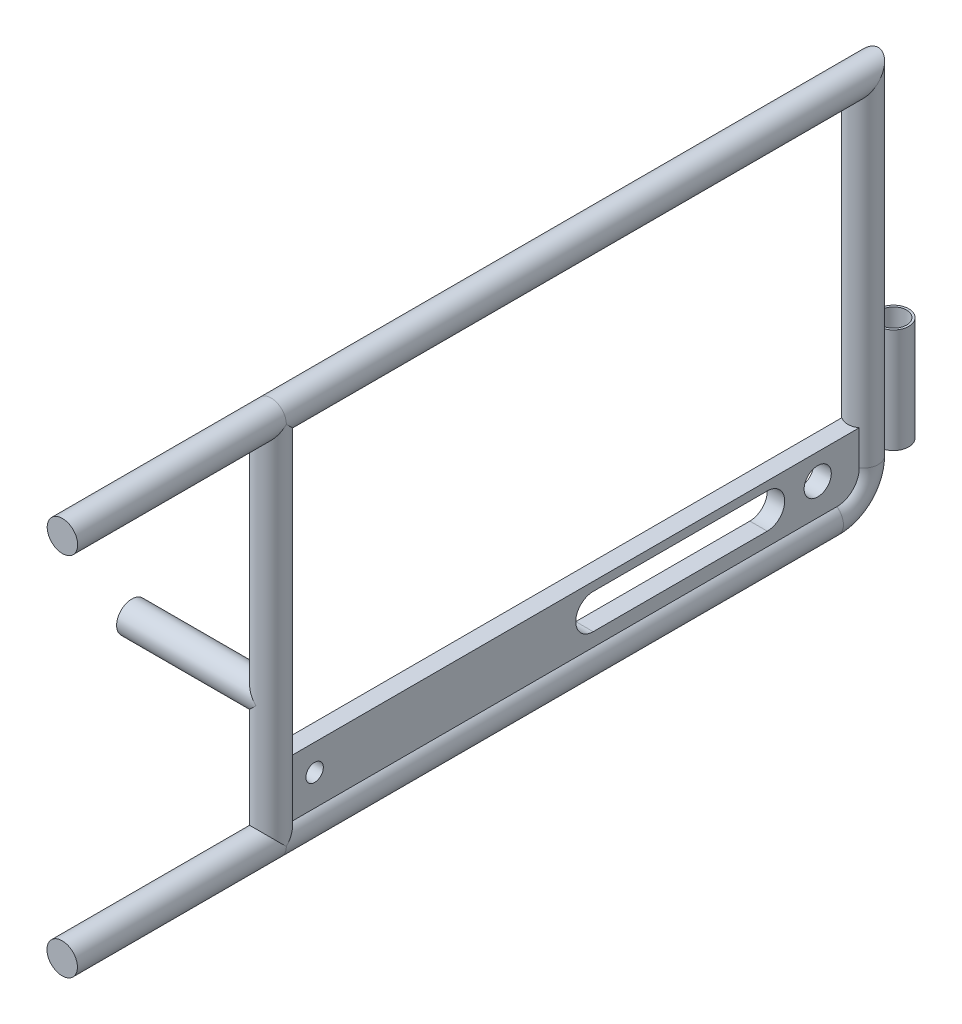
SolidWorks part; units mm, degrees
note: The reader was unsure of these and kept them because the rebuilt part matched: shared geometry of "Sketch3<8>", "Sketch1<23>".
ref_plane "Front Plane" through (0, 0, 0) normal (0, 0, 1) x (1, 0, 0)
ref_plane "Top Plane" through (0, 0, 0) normal (0, 1, 0) x (1, 0, 0)
ref_plane "Right Plane" through (0, 0, 0) normal (1, 0, 0) x (0, 0, -1)
sketch "Sketch1" plane through (0, 0, 0) normal (1, 0, 0) x (0, 0, -1)
  line L0 (126.1633, -30.1592) -> (152.2128, -152.4)
  line L2 (152.2128, -431.8) -> (584.0128, -431.8)
  line L4 (584.0128, -673.1) -> (584.0128, -431.8)
  line L5 (152.2128, -431.8) -> (0, -431.8)
  line L6 (558.6128, -698.5) -> (152.2128, -698.5)
  line L7 (88.9, 0) -> (0, 0)
  line L8 (152.2128, -152.4) -> (431.6128, -152.4)
  line L10 (457.0128, -177.8) -> (457.0128, -273.05)
  line L16 (457.0128, -273.05) -> (558.6128, -273.05)
  line L17 (584.0128, -298.45) -> (584.0128, -431.8)
  line L18 (-0.1872, -698.5) -> (152.2128, -698.5)
  line L19 (152.2128, -698.5) -> (152.2128, -431.8)
  line L20 (152.2128, -152.4) -> (152.2128, -431.8)
  arc A0 (88.9, 0) -> (126.1633, -30.1592) centre (88.9, -38.1) cw
  arc A1 (584.0128, -673.1) -> (558.6128, -698.5) centre (558.6128, -673.1) cw
  arc A2 (584.0128, -298.45) -> (558.6128, -273.05) centre (558.6128, -298.45) ccw
  arc A3 (431.6128, -152.4) -> (457.0128, -177.8) centre (431.6128, -177.8) cw
  point P5 (584.0128, -698.5)
  point P24 (584.0128, -273.05)
  point P30 (457.0128, -152.4)
  dimension "D2" = 38.1
  dimension "D11" = 25.4
  dimension "D9" = 25.4
  dimension "D1" = 88.9
  dimension "D3" = 120.65
  dimension "D4" = 431.8
  dimension "D5" = 431.8
  dimension "D6" = 279.4
  dimension "D7" = 152.4
  dimension "D8" = 546.1
  dimension "D10" = 127
  dimension "D17" = 124.9856
sketch "Sketch3" plane through (0, 0, 0) normal (0, 0, 1) x (1, 0, 0)
  circle A0 centre (0, -698.5) radius 11.1125
  dimension "D1" = 22.225
sweep "Sweep1" add profiles "Sketch3" path "Sketch1"
sweep "Sweep2" add profiles "Sketch3<8>" path "Sketch1<23>"
sketch "Sketch3<8>" plane through (0, 0, 0) normal (0, 0, 1) x (1, 0, 0) same geometry as "Sketch3"
sketch "Sketch1<23>" plane through (0, 0, 0) normal (1, 0, 0) x (0, 0, -1) same geometry as "Sketch1"
sketch "Sketch10" plane through (0, 0, 0) normal (1, 0, 0) x (0, 0, -1)
  line L1 (152.4, -914.4) -> (-272.7134, -914.4)
  line L2 (152.2128, -698.5) -> (152.2128, -431.8) construction
  circle A0 centre (152.2128, -609.6) radius 304.8
  dimension "D1" = 609.6
  dimension "D2" = 88.9
sketch "Sketch11" plane through (0, 0, 0) normal (1, 0, 0) x (0, 0, -1)
  line L0 (584.0128, -647.7) -> (152.2128, -647.7)
  line L1 (584.0128, -673.1) -> (584.0128, -431.8) construction
  line L2 (152.2128, -698.5) -> (152.2128, -431.8) construction
  line L3 (152.2128, -647.7) -> (152.2128, -698.5)
  line L4 (152.2128, -698.5) -> (558.6128, -698.5)
  line L5 (584.0128, -673.1) -> (584.0128, -647.7)
  line L6 (584.0128, -431.8) -> (584.0128, -482.6)
  line L7 (584.0128, -482.6) -> (152.2128, -482.6)
  line L8 (152.2128, -482.6) -> (152.2128, -431.8)
  line L9 (152.2128, -431.8) -> (584.0128, -431.8)
  line L10 (380.8128, -463.55) -> (177.6128, -666.75) construction
  line L11 (389.793, -472.5303) -> (186.593, -675.7303)
  line L12 (371.8325, -454.5697) -> (168.6325, -657.7697)
  line L13 (380.8128, -666.75) -> (177.6128, -463.55) construction
  line L14 (371.8325, -675.7303) -> (168.6325, -472.5303)
  line L15 (389.793, -657.7697) -> (186.593, -454.5697)
  line L16 (380.8128, -463.55) -> (507.8128, -463.55) construction
  line L17 (380.8128, -450.85) -> (507.8128, -450.85)
  line L18 (380.8128, -476.25) -> (507.8128, -476.25)
  line L19 (380.8128, -666.75) -> (507.8128, -666.75) construction
  line L20 (380.8128, -654.05) -> (507.8128, -654.05)
  line L21 (380.8128, -679.45) -> (507.8128, -679.45)
  line L22 (177.6128, -463.55) -> (177.6128, -666.75) construction
  line L23 (177.6128, -565.15) -> (446.4211, -666.75) construction
  line L24 (177.6128, -666.75) -> (446.4211, -565.15) construction
  line L25 (177.6128, -532.9233) -> (431.9175, -666.75) construction
  line L26 (431.9175, -666.75) -> (431.9175, -532.9233) construction
  line L27 (431.9175, -532.9233) -> (177.6128, -666.75) construction
  arc A0 (584.0128, -673.1) -> (558.6128, -698.5) centre (558.6128, -673.1) cw
  circle A1 centre (177.6128, -463.55) radius 6.35
  circle A2 centre (177.6128, -666.75) radius 6.35
  circle A3 centre (279.2128, -565.15) radius 6.35
  arc A4 (380.8128, -450.85) -> (380.8128, -476.25) centre (380.8128, -463.55) ccw
  arc A5 (389.793, -472.5303) -> (371.8325, -454.5697) centre (380.8128, -463.55) ccw
  arc A6 (168.6325, -657.7697) -> (186.593, -675.7303) centre (177.6128, -666.75) ccw
  arc A7 (371.8325, -675.7303) -> (389.793, -657.7697) centre (380.8128, -666.75) ccw
  arc A8 (186.593, -454.5697) -> (168.6325, -472.5303) centre (177.6128, -463.55) ccw
  arc A9 (507.8128, -476.25) -> (507.8128, -450.85) centre (507.8128, -463.55) ccw
  arc A10 (380.8128, -654.05) -> (380.8128, -679.45) centre (380.8128, -666.75) ccw
  arc A11 (507.8128, -679.45) -> (507.8128, -654.05) centre (507.8128, -666.75) ccw
  arc A12 (380.8128, -463.55) -> (464.982, -666.75) centre (177.6064, -666.7541) cw
  point P12 (584.0128, -698.5)
  point P27 (279.2128, -565.15)
  point P32 (279.2128, -565.15)
  point P39 (444.3128, -463.55)
  point P44 (444.3128, -666.75)
  dimension "D1" = 25.4
  dimension "D4" = 12.7
  dimension "D5" = 12.7
  dimension "D8" = 12.7
  dimension "D12" = 287.3756
  dimension "D2" = 50.8
  dimension "D3" = 50.8
  dimension "D6" = 19.05
  dimension "D7" = 19.05
  dimension "D9" = 90
  dimension "D10" = 25.4
  dimension "D11" = 76.2
extrude "Boss-Extrude2" add sketch "Sketch11" along normal mid plane 12.7 contours A2 | L0 L3 L4 A0 L5 | L21 A11 L20 A10
sketch "Sketch12" plane through (0, 0, 0) normal (1, 0, 0) x (0, 0, -1)
  circle A0 centre (152.2128, -609.6) radius 11.1125
  circle A1 centre (152.2128, -609.6) radius 9.525
  dimension "D1" = 19.05
  dimension "D2" = 22.225
extrude "Boss-Extrude3" add sketch "Sketch12" against normal blind 101.6
ref_plane "Plane1" through (0, -673.1, 0) normal (0, 1, 0) x (1, 0, 0)
sketch "Sketch13" plane through (0, -673.1, 0) normal (0, 1, 0) x (1, 0, 0)
  circle A0 centre (0, 606.2378) radius 11.1125
  circle A1 centre (0, 606.2378) radius 9.525
  arc A2 (6.35, 574.8933) -> (-6.35, 574.8933) centre (0, 584.0128) ccw construction
  dimension "D1" = 19.05
  dimension "D2" = 22.225
extrude "Boss-Extrude4" add sketch "Sketch13" along normal blind 76.2 separate body
sketch "Sketch14" plane through (0, 0, 0) normal (1, 0, 0) x (0, 0, -1)
  line L1 (574.8933, -647.7) -> (574.8933, -673.1) construction
  line L2 (558.6128, -689.3805) -> (161.3323, -689.3805) construction
  circle A0 centre (544.5911, -666.3173) radius 9.906
  dimension "D1" = 19.812
  dimension "D3" = 23.0632
  dimension "D2" = 30.3022
extrude "Cut-Extrude1" cut sketch "Sketch14" against normal through all both and the other way through all contours A0
